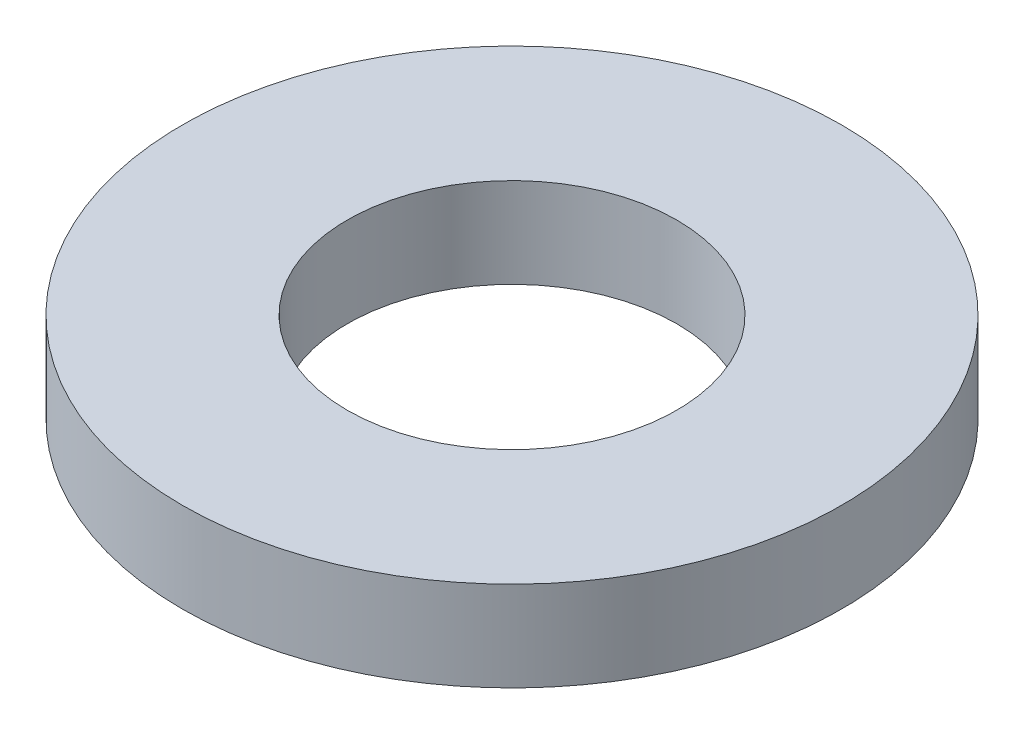
SolidWorks part; units mm, degrees
ref_plane "Front Plane" through (0, 0, 0) normal (0, 0, 1) x (1, 0, 0)
ref_plane "Top Plane" through (0, 0, 0) normal (0, 1, 0) x (1, 0, 0)
ref_plane "Right Plane" through (0, 0, 0) normal (1, 0, 0) x (0, 0, -1)
sketch "Sketch1" plane through (0, 0, 0) normal (0, 1, 0) x (1, 0, 0)
  circle A0 centre (0, 0) radius 55
  dimension "FLANGE_OD" = 110
extrude "Boss-Extrude1" add sketch "Sketch1" along normal blind 15
sketch "Sketch2" plane through (0, 0, 0) normal (0, 1, 0) x (1, 0, 0)
  circle A0 centre (0, 0) radius 27.5
  dimension "BORE_D" = 55
extrude "Cut-Extrude1" cut sketch "Sketch2" along normal through all
sketch "Sketch3" plane through (0, 15, 0) normal (0, 1, 0) x (1, 0, 0)
  circle A0 centre (0, 0) radius 22.773 construction
  circle A1 centre (-22.773, 0) radius 2.3776
  dimension "BOLT_D" = 4.7553
  dimension "BOLT_PCD" = 45.546
extrude "Cut-Extrude2" cut sketch "Sketch3" against normal blind 10.6841 rebuild error yes
pattern_circular "CirPattern1" count 4 over 360 rebuild error yes
